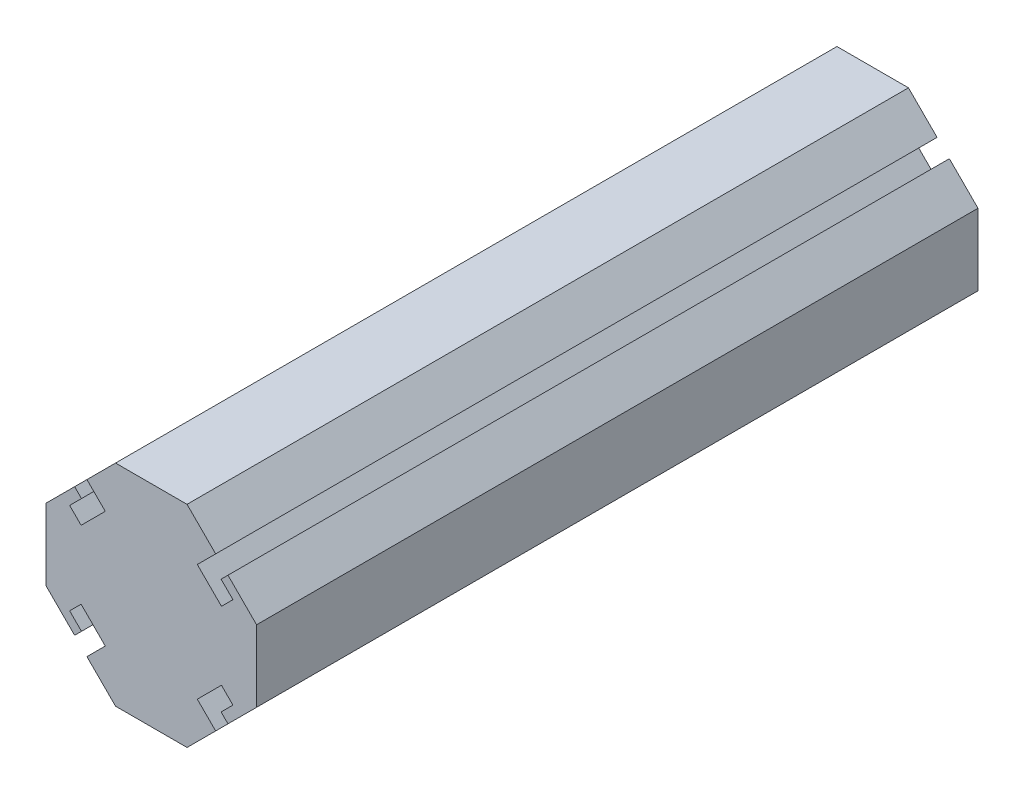
SolidWorks part; units mm, degrees
ref_plane "Спереди" through (0, 0, 0) normal (0, 0, 1) x (1, 0, 0)
ref_plane "Сверху" through (0, 0, 0) normal (0, 1, 0) x (1, 0, 0)
ref_plane "Справа" through (0, 0, 0) normal (1, 0, 0) x (0, 0, -1)
sketch "Эскиз1" plane through (0, 0, 0) normal (0, 0, 1) x (1, 0, 0)
  line L0 (-47.2719, 0) -> (56.8927, 0) construction
  line L1 (0, 53.9243) -> (0, -61.466) construction
  line L2 (-36.4884, 12.3899) -> (-36.4884, -12.3899)
  line L3 (-12.3899, -36.4884) -> (-22.3078, -26.5706)
  line L4 (-12.3899, -36.4884) -> (12.3899, -36.4884)
  line L5 (-22.3078, -26.5706) -> (-15.9488, -20.2116)
  line L6 (-15.9488, -20.2116) -> (-24.3171, -11.8432)
  line L7 (-24.3171, -11.8432) -> (-28.2949, -15.821)
  line L8 (-28.2949, -15.821) -> (-24.1894, -19.9266)
  line L9 (-36.4884, -12.3899) -> (-26.5706, -22.3078)
  line L10 (-26.5706, -22.3078) -> (-24.1894, -19.9266)
  line L11 (-36.4884, 12.3899) -> (-26.5706, 22.3078)
  line L12 (-26.5706, 22.3078) -> (-24.1894, 19.9266)
  line L13 (-28.2949, 15.821) -> (-24.1894, 19.9266)
  line L14 (-24.3171, 11.8432) -> (-28.2949, 15.821)
  line L15 (-15.9488, 20.2116) -> (-24.3171, 11.8432)
  line L16 (-22.3078, 26.5706) -> (-15.9488, 20.2116)
  line L17 (-12.3899, 36.4884) -> (-22.3078, 26.5706)
  line L18 (-12.3899, 36.4884) -> (12.3899, 36.4884)
  line L19 (12.3899, 36.4884) -> (22.3078, 26.5706)
  line L20 (22.3078, 26.5706) -> (15.9488, 20.2116)
  line L21 (15.9488, 20.2116) -> (24.3171, 11.8432)
  line L22 (24.3171, 11.8432) -> (28.2949, 15.821)
  line L23 (28.2949, 15.821) -> (24.1894, 19.9266)
  line L24 (26.5706, 22.3078) -> (24.1894, 19.9266)
  line L25 (36.4884, 12.3899) -> (26.5706, 22.3078)
  line L26 (26.5706, -22.3078) -> (24.1894, -19.9266)
  line L27 (36.4884, -12.3899) -> (26.5706, -22.3078)
  line L28 (28.2949, -15.821) -> (24.1894, -19.9266)
  line L29 (24.3171, -11.8432) -> (28.2949, -15.821)
  line L30 (15.9488, -20.2116) -> (24.3171, -11.8432)
  line L31 (22.3078, -26.5706) -> (15.9488, -20.2116)
  line L32 (12.3899, -36.4884) -> (22.3078, -26.5706)
  line L33 (36.4884, 12.3899) -> (36.4884, -12.3899)
  point P9 (22.3078, -26.5706)
  point P16 (-36.4884, 0)
  point P25 (0, 36.4884)
  point P40 (0, -36.4884)
extrude "Бобышка-Вытянуть1" add sketch "Эскиз1" against normal blind 250
sketch "Эскиз3" plane through (0, 0, 0) normal (0, 0, 1) x (1, 0, 0)
  line L0 (0, 26.6724) -> (0, -55.4933) construction
  line L1 (-52.3974, -14.7857) -> (-1.5991, -14.7857) construction
  line L2 (0, 1.6538) -> (16.4579, -14.7857)
  line L3 (16.4579, -14.7857) -> (0, -31.2253)
  line L4 (0, -31.2253) -> (-16.4579, -14.7857)
  line L5 (-16.4579, -14.7857) -> (0, 1.6538)
  circle A0 centre (16.4579, -14.7857) radius 10
  circle A1 centre (0, 1.6538) radius 10
  circle A2 centre (-16.4579, -14.7857) radius 10
  circle A3 centre (0, -31.2253) radius 10
  point P13 (0, 0)
  point P14 (16.4579, -14.7857)
  dimension "D1" = 20
  dimension "D2" = 20
  dimension "D3" = 20
  dimension "D4" = 20
  dimension "D7" = 12.9158
